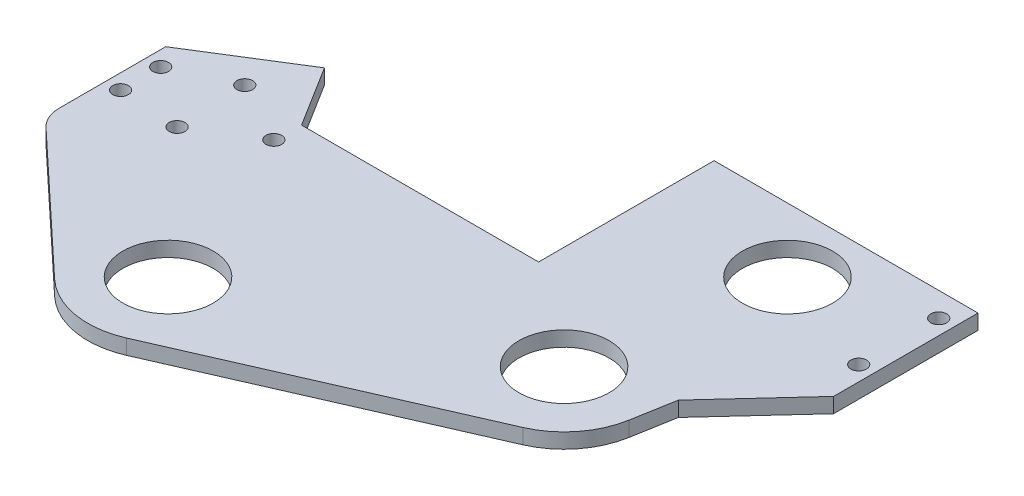
SolidWorks part; units mm, degrees
ref_plane "Front Plane" through (0, 0, 0) normal (0, 0, 1) x (1, 0, 0)
ref_plane "Top Plane" through (0, 0, 0) normal (0, 1, 0) x (1, 0, 0)
ref_plane "Right Plane" through (0, 0, 0) normal (1, 0, 0) x (0, 0, -1)
sketch "Sketch1" plane through (0, 0, 0) normal (0, 1, 0) x (1, 0, 0)
  line L1 (-62.0695, -79.8953) -> (25.163, -41.6958)
  line L5 (39.9361, -22.8907) -> (42.2711, -9.5867)
  line L6 (42.2711, -9.5867) -> (65.827, 16.0128)
  line L12 (-135.7856, -31.9357) -> (-135.7856, 6.1643)
  line L16 (-92.7763, 6.1642) -> (-17.7344, 6.1642)
  line L17 (-135.7856, -31.9357) -> (-89.6201, -75.1681)
  line L19 (65.8268, 61.7268) -> (-17.7344, 61.7268)
  line L20 (65.827, 16.0128) -> (65.8268, 61.7268)
  line L22 (-17.7344, 61.7268) -> (-17.7344, 6.1642)
  line L23 (-135.7856, 6.1643) -> (-104.8541, 25.4925)
  line L24 (-218.6332, 207.5761) -> (-71.6499, -27.6449) construction
  line L25 (-104.8541, 25.4925) -> (-92.7763, 6.1642)
  circle A0 centre (25.8218, 41.4126) radius 14.29
  circle A1 centre (15.0126, -18.5165) radius 14.29
  circle A2 centre (-72.2583, -56.6285) radius 14.29
  arc A4 (39.9361, -22.8907) -> (25.163, -41.6958) centre (15.0127, -18.5164) cw
  arc A6 (-62.0695, -79.8953) -> (-89.6201, -75.1681) centre (-72.2582, -56.6283) cw
  point P11 (-62.0695, -79.8953)
extrude "Boss-Extrude1" add sketch "Sketch1" along normal blind 4.7625
fillet "Fillet1" radius 10 1 edges at (-135.7856, 2.3813, 31.9357)
hole_wizard "#10 Clearance Hole1" positions "Sketch2" profile "Sketch3" hole size "#10" standard "ANSI Inch" end condition through all
sketch "Sketch2" plane through (0, 4.7625, 0) normal (0, 1, 0) x (1, 0, 0)
  point P0 (61.0644, 54.0575)
  point P3 (61.0644, 28.7127)
  point P7 (-131.0231, -0.1858)
  point P10 (-131.0231, -12.8858)
sketch "Sketch3" plane through (61.0644, 4.7625, -54.0575) normal (1, 0, 0) x (0, 0, 1)
  line L0 (0, 0) -> (0, 4.7625)
  line L1 (0, 4.7625) -> (2.4892, 4.7625)
  line L2 (2.4892, 4.7625) -> (2.4892, 0)
  line L5 (2.4892, 0) -> (0, 0)
  line L11 (0, -6.35) -> (0, 107.95) construction
  dimension "Thru Hole Dia." = 4.9784
  dimension "Thru Hole Depth" = 4.7625
sketch "Sketch4" plane through (0, 4.7625, 0) normal (0, 1, 0) x (1, 0, 0)
  line L0 (-72.2583, -56.6285) -> (-102.5433, -8.1626) construction
  line L1 (-102.5433, -8.1626) -> (-93.1194, -2.2738) construction
  line L2 (-102.5433, -8.1626) -> (-111.9673, -14.0514) construction
  line L3 (-102.5433, -8.1626) -> (-112.7326, 8.1435) construction
  line L4 (-102.5433, -8.1626) -> (-186.6684, 126.4648) construction
  line L5 (65.8269, 41.4127) -> (65.8269, 28.7127) construction
  dimension "D1" = 57.15
  dimension "D2" = 22.225
  dimension "D3" = 32
hole_wizard "#10 Clearance Hole2" positions "Sketch5" profile "Sketch6" hole size "#10" standard "ANSI Inch" end condition through all
sketch "Sketch5" plane through (0, 4.7625, 0) normal (0, 1, 0) x (1, 0, 0)
  point P0 (-111.9673, -14.0514)
  point P3 (-93.1194, -2.2738)
  point P7 (-112.7326, 8.1435)
sketch "Sketch6" plane through (-111.9673, 4.7625, 14.0514) normal (1, 0, 0) x (0, 0, 1)
  line L0 (0, 0) -> (0, 4.7625)
  line L1 (0, 4.7625) -> (2.4892, 4.7625)
  line L2 (2.4892, 4.7625) -> (2.4892, 0)
  line L5 (2.4892, 0) -> (0, 0)
  line L11 (0, -6.35) -> (0, 107.95) construction
  dimension "Thru Hole Dia." = 4.9784
  dimension "Thru Hole Depth" = 4.7625
